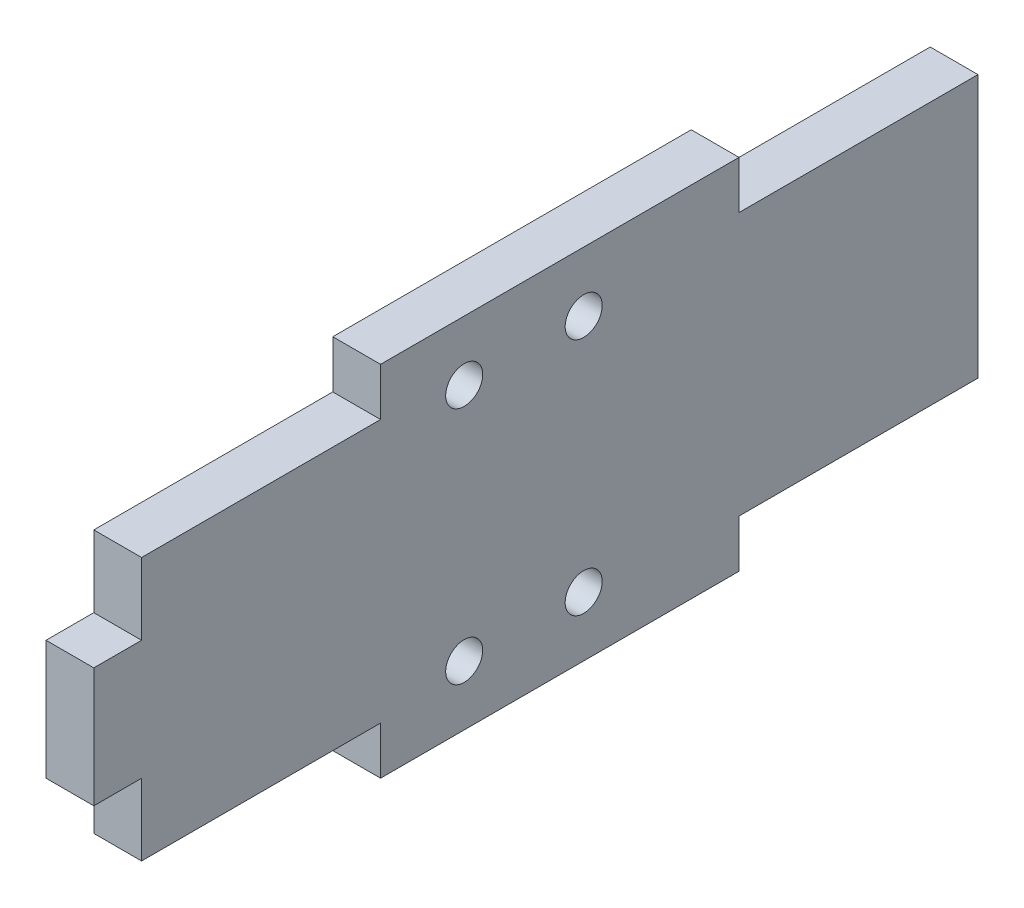
SolidWorks part; units mm, degrees
ref_plane "Front" through (0, 0, 0) normal (0, 0, 1) x (1, 0, 0)
ref_plane "Top" through (0, 0, 0) normal (0, 1, 0) x (1, 0, 0)
ref_plane "Right" through (0, 0, 0) normal (1, 0, 0) x (0, 0, -1)
sketch "Skizze1" plane through (0, 0, 0) normal (1, 0, 0) x (0, 0, -1)
  line L0 (0, 0) -> (74, 0) construction
  line L1 (0, -5) -> (0, 5)
  line L2 (0, 5) -> (4, 5)
  line L3 (4, 5) -> (4, 15)
  line L4 (4, 15) -> (74, 15)
  line L5 (74, 15) -> (74, -15)
  line L6 (4, -15) -> (74, -15)
  line L7 (4, -5) -> (4, -15)
  line L8 (0, -5) -> (4, -5)
  dimension "D1" = 4
  dimension "D2" = 10
  dimension "D3" = 30
  dimension "D4" = 70
extrude "Aufsatz-Linear austragen1" add sketch "Skizze1" along normal blind 4
sketch "Skizze2" plane through (4, 0, 0) normal (1, 0, 0) x (0, 0, -1)
  line L0 (39, 15) -> (39, 0) construction
  line L1 (4, 15) -> (24, 15)
  line L2 (4, 15) -> (4, 11)
  line L3 (4, 11) -> (24, 11)
  line L4 (24, 15) -> (24, 11)
  line L5 (74, 15) -> (54, 15)
  line L6 (74, 15) -> (74, 11)
  line L7 (74, 11) -> (54, 11)
  line L8 (54, 15) -> (54, 11)
  line L9 (74, 15) -> (4, 15) construction
  line L10 (39, 0) -> (0, 0) construction
  line L11 (54, -15) -> (54, -11)
  line L12 (74, -11) -> (54, -11)
  line L13 (74, -15) -> (74, -11)
  line L14 (74, -15) -> (54, -15)
  line L15 (24, -15) -> (24, -11)
  line L16 (4, -11) -> (24, -11)
  line L17 (4, -15) -> (4, -11)
  line L18 (4, -15) -> (24, -15)
  dimension "D1" = 4
  dimension "D2" = 30
extrude "Schnitt-Linear austragen1" cut sketch "Skizze2" against normal through all
sketch "Skizze3" [suppressed] plane through (4, 0, 0) normal (1, 0, 0) x (0, 0, -1)
  line L0 (74, 15) -> (4, 15) construction
  line L1 (24, 15) -> (54, 15)
  line L2 (24, 15) -> (24, 11)
  line L3 (24, 11) -> (54, 11)
  line L4 (54, 15) -> (54, 11)
  line L5 (39, -15) -> (39, 11) construction
  line L6 (4, -15) -> (74, -15) construction
  dimension "D1" = 4
  dimension "D2" = 30
extrude "Schnitt-Linear austragen2" [suppressed] cut sketch "Skizze3" against normal through all
sketch "Skizze4" plane through (4, 0, 0) normal (1, 0, 0) x (0, 0, -1)
  line L0 (0, 0) -> (36, 0) construction
  line L1 (41, 10) -> (31, 10) construction
  line L2 (41, 10) -> (41, -10) construction
  line L3 (41, -10) -> (31, -10) construction
  line L4 (31, 10) -> (31, -10) construction
  line L5 (41, 10) -> (31, -10) construction
  line L6 (41, -10) -> (31, 10) construction
  line L7 (0, 5) -> (0, -5) construction
  circle A0 centre (41, 10) radius 1.55
  circle A1 centre (31, 10) radius 1.55
  circle A2 centre (31, -10) radius 1.55
  circle A3 centre (41, -10) radius 1.55
  point P0 (36, 0)
  dimension "D3" = 3.1
  dimension "D1" = 10
  dimension "D2" = 20
  dimension "D4" = 36
extrude "Schnitt-Linear austragen3" cut sketch "Skizze4" against normal blind 10
